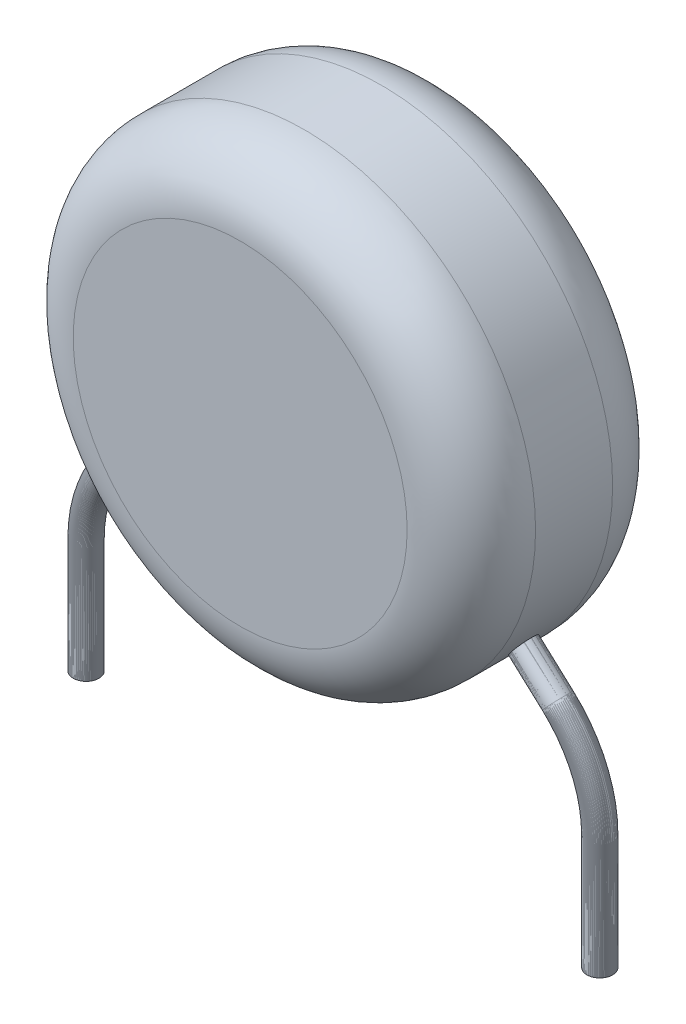
SolidWorks part; units mm, degrees
ref_plane "Спереди" through (0, 0, 0) normal (0, 0, 1) x (1, 0, 0)
ref_plane "Сверху" through (0, 0, 0) normal (0, 1, 0) x (1, 0, 0)
ref_plane "Справа" through (0, 0, 0) normal (1, 0, 0) x (0, 0, -1)
sketch "Эскиз1" plane through (0, 0, 0) normal (0, 0, 1) x (1, 0, 0)
  line L0 (0, 0) -> (0, 51.7005) construction
  circle A0 centre (0, 15) radius 9
  dimension "D1" = 18
  dimension "D2" = 15
extrude "Вытянуть1" add sketch "Эскиз1" along normal blind 4 and the other way blind 4
sketch "Эскиз2" plane through (0, 0, 0) normal (0, 0, 1) x (1, 0, 0)
  line L0 (0, 0) -> (-20.5141, 0) construction
  line L1 (0, 0) -> (0, 20.3292) construction
  line L2 (-10, 0) -> (-10, 4.4836)
  line L3 (-8.3677, 8.1794) -> (-2.4984, 13.5278)
  line L5 (2.4984, 13.5278) -> (8.3677, 8.1794)
  line L6 (10, 4.4836) -> (10, 0)
  arc A0 (-10, 4.4836) -> (-8.3677, 8.1794) centre (-5, 4.4836) cw
  arc A1 (8.3677, 8.1794) -> (10, 4.4836) centre (5, 4.4836) cw
  arc A2 (-2.4984, 13.5278) -> (-0.149, 14.7272) centre (0.8694, 9.832) cw
  arc A3 (0.149, 14.7272) -> (2.4984, 13.5278) centre (-0.8694, 9.832) cw
  arc A4 (0.149, 14.7272) -> (-0.149, 14.7272) centre (0, 14.011) ccw
  dimension "D2" = 5
  dimension "D1" = 20
sketch "Эскиз3" plane through (0, 0, 0) normal (0, 1, 0) x (1, 0, 0)
  line L0 (-8.3677, 0) -> (-2.4984, 0) construction
  line L1 (0, 0) -> (-20.5141, 0) construction
  line L2 (8.3677, 0) -> (10, 0) construction
  circle A0 centre (-10, 0) radius 0.5
  circle A1 centre (10, 0) radius 0.5
  dimension "D1" = 1
  dimension "D3" = 10
  dimension "D2" = 20
extrude "Вытянуть2" add sketch "Эскиз3" along normal blind 4.48
surface "Поверхность-По траектории2"
sketch "Эскиз3<4>" plane through (0, 0, 0) normal (0, 1, 0) x (1, 0, 0) same geometry as "Эскиз3"
fillet "Скругление1" radius 2.5 2 edges at (9, 15, -4) (9, 15, 4)
